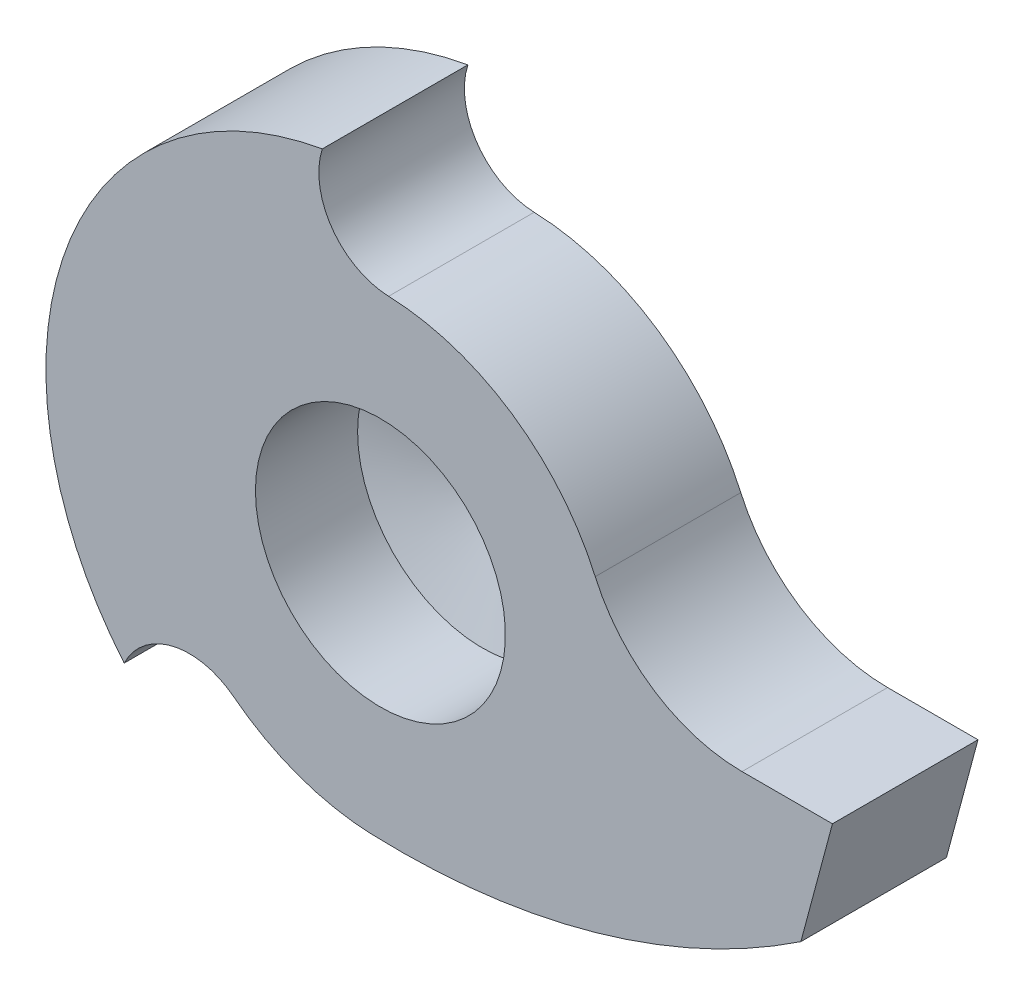
SolidWorks part; units mm, degrees
ref_plane "Front Plane" through (0, 0, 0) normal (0, 0, 1) x (1, 0, 0)
ref_plane "Top Plane" through (0, 0, 0) normal (0, 1, 0) x (1, 0, 0)
ref_plane "Right Plane" through (0, 0, 0) normal (1, 0, 0) x (0, 0, -1)
sketch "Sketch1" plane through (0, 0, 0) normal (0, 0, 1) x (1, 0, 0)
  line L0 (0, 0) -> (50, 0) construction
  line L1 (50, 0) -> (40, 0)
  line L2 (50, 0) -> (46.5059, -13.04)
  line L3 (-28.3436, -23.7831) -> (0, 0) construction
  line L4 (0, 0) -> (-6.425, 36.4379) construction
  line L5 (0, 0) -> (-34.7686, 12.6547) construction
  circle A0 centre (0, 0) radius 50 construction
  circle A1 centre (0, 0) radius 13.825 construction
  arc A2 (40, 0) -> (23.761, 10.5554) centre (40, 17.7692) cw
  arc A10 (-28.3436, -23.7831) -> (-6.425, 36.4379) centre (0, 0) cw
  arc A11 (23.761, 10.5554) -> (0.9083, 25.9841) centre (0, 0) ccw
  arc A12 (-6.425, 36.4379) -> (0.9083, 25.9841) centre (1.1878, 33.9792) ccw
  arc A13 (-28.3436, -23.7831) -> (-16.2384, -20.9419) centre (-21.1406, -27.264) cw
  arc A14 (-16.2384, -20.9419) -> (-1.0084, -26.4808) centre (0, 0) ccw
  arc A15 (-1.0084, -26.4808) -> (46.5059, -13.04) centre (2.0359, 53.4612) ccw
  dimension "D1" = 100
  dimension "D2" = 27.65
  dimension "D6" = 26
  dimension "D7" = 13
  dimension "D8" = 120
  dimension "D9" = 8
  dimension "D10" = 160
  dimension "D11" = 26.5
  dimension "D12" = 8
  dimension "D13" = 80
  dimension "D3" = 75
  dimension "D4" = 13.5
  dimension "D5" = 10
extrude "Boss-Extrude1" add sketch "Sketch1" along normal blind 16.1
sketch "Sketch2" plane through (0, 0, 0) normal (0, 1, 0) x (1, 0, 0)
  line L0 (13.825, -16.1) -> (13.825, -4.8)
  line L2 (13.825, -4.8) -> (5, -2.2)
  line L3 (5, -2.2) -> (2.75, -2.2)
  line L4 (2.75, -2.2) -> (2.75, 0)
  line L5 (-50, 0) -> (50, 0) construction
  line L6 (2.75, 0) -> (0, 0)
  line L7 (0, 0) -> (0, -16.1)
  line L8 (0, -16.1) -> (13.825, -16.1)
  line L9 (-13.825, 0) -> (13.825, 0) construction
  line L10 (-13.825, 0) -> (13.825, 0) construction
  line L11 (23.761, -16.1) -> (40, -16.1) construction
  dimension "D1" = 11.3
  dimension "D2" = 13.9
  dimension "D3" = 5
  dimension "D4" = 2.75
revolve "Cut-Revolve1" cut sketch "Sketch2" angle 360 about L7
ref_plane "Plane1" through (0, 0, 8.05) normal (0, 0, 1) x (1, 0, 0)
